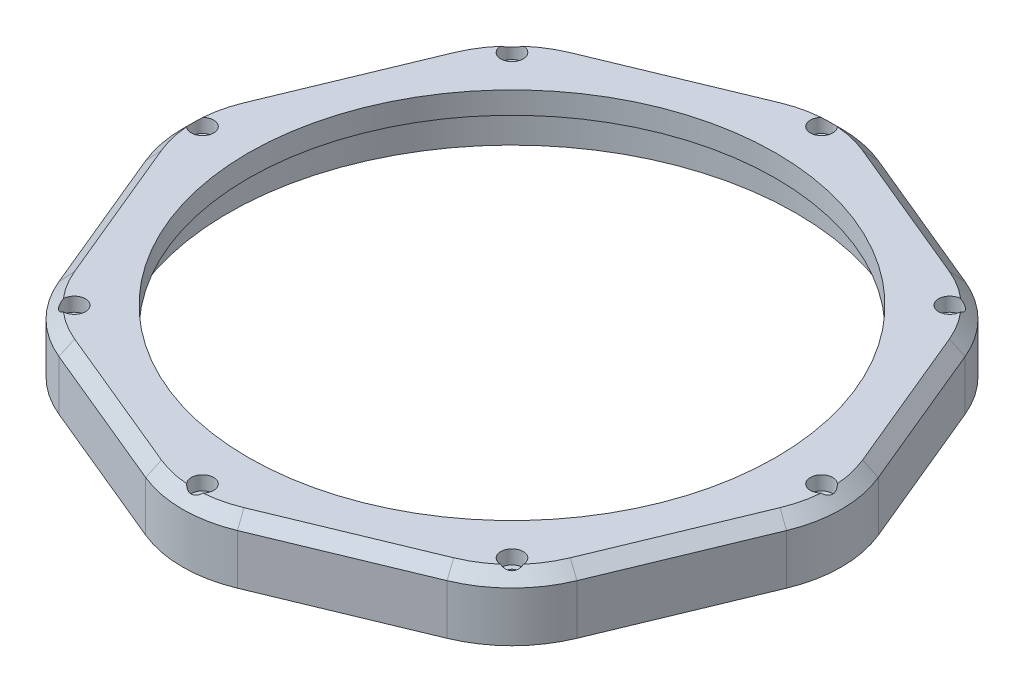
SolidWorks part; units mm, degrees
ref_plane "Front Plane" through (0, 0, 0) normal (0, 0, 1) x (1, 0, 0)
ref_plane "Top Plane" through (0, 0, 0) normal (0, 1, 0) x (1, 0, 0)
ref_plane "Right Plane" through (0, 0, 0) normal (1, 0, 0) x (0, 0, -1)
sketch "Sketch1" plane through (0, 0, 0) normal (0, 1, 0) x (1, 0, 0)
  line L0 (0, 0) -> (0, -84.9266) construction
  line L1 (80.1712, 11.4805) -> (64.8075, 48.5717)
  line L2 (48.5717, 64.8075) -> (11.4805, 80.1712)
  line L3 (-11.4805, 80.1712) -> (-48.5717, 64.8075)
  line L4 (-64.8075, 48.5717) -> (-80.1712, 11.4805)
  line L5 (-80.1712, -11.4805) -> (-64.8075, -48.5717)
  line L6 (-48.5717, -64.8075) -> (-11.4805, -80.1712)
  line L7 (11.4805, -80.1712) -> (48.5717, -64.8075)
  line L8 (64.8075, -48.5717) -> (80.1712, -11.4805)
  line L9 (0, -84.9266) -> (0, -85.3997) construction
  line L19 (-77.4548, 0) -> (-54.7688, -54.7688) construction
  line L20 (-54.7688, -54.7688) -> (0, -77.4548) construction
  line L21 (0, -77.4548) -> (54.7688, -54.7688) construction
  line L22 (54.7688, -54.7688) -> (77.4548, 0) construction
  line L23 (77.4548, 0) -> (54.7688, 54.7688) construction
  line L24 (54.7688, 54.7688) -> (0, 77.4548) construction
  line L25 (0, 77.4548) -> (-54.7688, 54.7688) construction
  line L26 (-54.7688, 54.7688) -> (-77.4548, 0) construction
  circle A0 centre (0, 0) radius 78.4619 construction
  arc A1 (-64.8075, -48.5717) -> (-48.5717, -64.8075) centre (-37.0912, -37.0912) ccw
  arc A2 (-80.1712, 11.4805) -> (-80.1712, -11.4805) centre (-52.4548, 0) ccw
  arc A3 (-48.5717, 64.8075) -> (-64.8075, 48.5717) centre (-37.0912, 37.0912) ccw
  arc A4 (11.4805, 80.1712) -> (-11.4805, 80.1712) centre (0, 52.4548) ccw
  arc A5 (64.8075, 48.5717) -> (48.5717, 64.8075) centre (37.0912, 37.0912) ccw
  arc A6 (80.1712, 11.4805) -> (80.1712, -11.4805) centre (52.4548, 0) cw
  arc A7 (48.5717, -64.8075) -> (64.8075, -48.5717) centre (37.0912, -37.0912) ccw
  arc A8 (-11.4805, -80.1712) -> (11.4805, -80.1712) centre (0, -52.4548) ccw
  circle A9 centre (0, 0) radius 71.5589 construction
  circle A21 centre (-54.7688, 54.7688) radius 1.5
  circle A22 centre (-54.7688, 54.7688) radius 2.8
  circle A23 centre (0, 77.4548) radius 1.5
  circle A24 centre (0, 77.4548) radius 2.8
  circle A25 centre (54.7688, 54.7688) radius 1.5
  circle A26 centre (54.7688, 54.7688) radius 2.8
  circle A27 centre (77.4548, 0) radius 1.5
  circle A28 centre (77.4548, 0) radius 2.8
  circle A29 centre (54.7688, -54.7688) radius 1.5
  circle A30 centre (54.7688, -54.7688) radius 2.8
  circle A31 centre (0, -77.4548) radius 1.5
  circle A32 centre (0, -77.4548) radius 2.8
  circle A33 centre (-54.7688, -54.7688) radius 1.5
  circle A34 centre (-54.7688, -54.7688) radius 2.8
  circle A35 centre (-77.4548, 0) radius 1.5
  circle A36 centre (-77.4548, 0) radius 2.8
  circle A37 centre (0, 0) radius 66
  point P15 (-84.9266, 0)
  point P18 (-60.0522, 60.0522)
  point P42 (0, -81.6794)
  point P43 (-58.3044, 58.3044)
  point P67 (0, 0)
  dimension "D2" = 30
  dimension "D4" = 5.6
  dimension "D3" = 3
  dimension "D5" = 5
  dimension "D7" = 132
  dimension "D1" = 65
  dimension "D6" = 8
extrude "Boss-Extrude1" add sketch "Sketch1" along normal blind 15.5 contours L6 A8 L7 A7 L8 A6 L1 A5 L2 A4 L3 A3 L4 A2 L5 A1 A37 A36 A34 A32 A30 A28 A26 A24 A22 | A34 A33 | A36 A35 | A22 A21 | A24 A23 | A26 A25 | A28 A27 | A30 A29 | A32 A31 region at (82.2216, 0, 0) region at (-57.4896, 0, -54.7688) region at (-2.7208, 0, -77.4548) region at (52.048, 0, -54.7688) region at (74.734, 0, 0) region at (52.048, 0, 54.7688) region at (-2.7208, 0, 77.4548) region at (-57.4896, 0, 54.7688) region at (-80.1756, 0, 0)
sketch "Sketch2" plane through (0, 0, 0) normal (0, -1, 0) x (1, 0, 0)
  circle A0 centre (0, 0) radius 71
  dimension "D1" = 142
extrude "Cut-Extrude1" cut sketch "Sketch2" against normal blind 10
chamfer "Chamfer1" distance 3 angle 45 16 edges at (-72.4894, 15.5, 30.0261) (-58.3044, 15.5, 58.3044) (-82.4548, 15.5, 0) (-30.0261, 15.5, 72.4894) (-72.4894, 15.5, -30.0261) (0, 15.5, 82.4548) (-58.3044, 15.5, -58.3044) (30.0261, 15.5, 72.4894) (-30.0261, 15.5, -72.4894) (58.3044, 15.5, 58.3044) (0, 15.5, -82.4548) (72.4894, 15.5, 30.0261) (30.0261, 15.5, -72.4894) (82.4548, 15.5, 0) (58.3044, 15.5, -58.3044) (72.4894, 15.5, -30.0261)
extrude "Cut-Extrude2" cut sketch "Sketch1<6>" against normal blind 3.5 from surface contours A34 A33 | A32 A31 | A30 A29 | A28 A27 | A26 A25 | A24 A23 | A22 A21 | A36 A35 region at (-57.4896, 0, -54.7688) region at (-2.7208, 0, -77.4548) region at (52.048, 0, -54.7688) region at (74.734, 0, 0) region at (52.048, 0, 54.7688) region at (-2.7208, 0, 77.4548) region at (-57.4896, 0, 54.7688) region at (-80.1756, 0, 0) starting at face at (0, 15.5, 0)
sketch "Sketch1<6>" plane through (0, 0, 0) normal (0, 1, 0) x (1, 0, 0) same geometry as "Sketch1"
